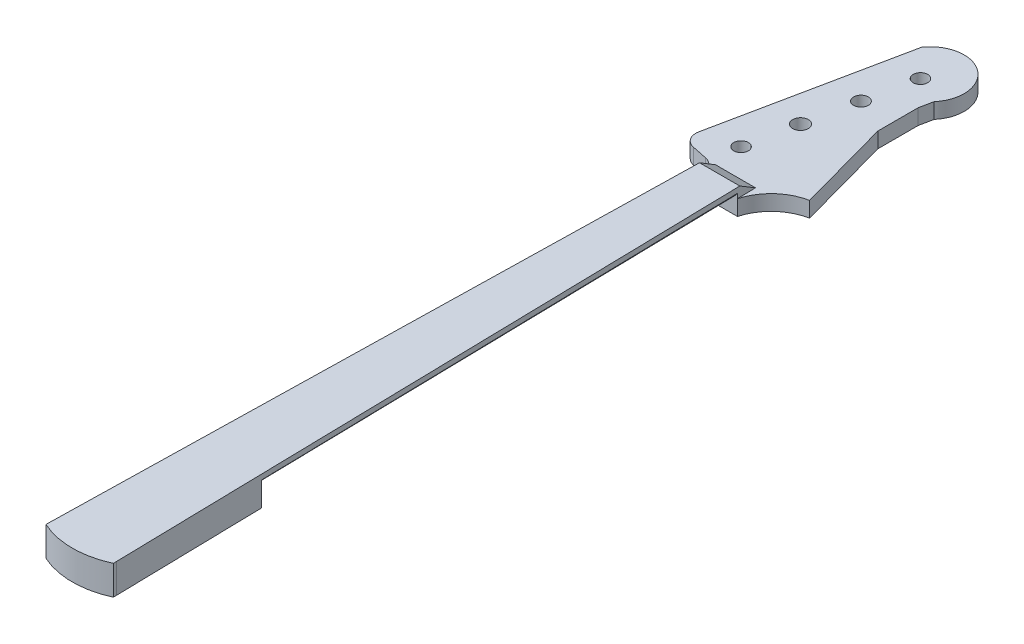
SolidWorks part; units mm, degrees
ref_plane "Front Plane" through (0, 0, 0) normal (0, 0, 1) x (1, 0, 0)
ref_plane "Top Plane" through (0, 0, 0) normal (0, 1, 0) x (1, 0, 0)
ref_plane "Right Plane" through (0, 0, 0) normal (1, 0, 0) x (0, 0, -1)
sketch "Sketch1" plane through (0, 0, 0) normal (0, 0, 1) x (1, 0, 0)
  line L0 (-19.05, 0) -> (19.05, 0)
  line L1 (19.05, 0) -> (19.05, -4.826)
  line L2 (19.05, -4.826) -> (-19.05, -4.826)
  line L3 (-19.05, -4.826) -> (-19.05, 0)
  point P3 (-19.5158, 0.0762)
  point P6 (0, 0)
  dimension "D1" = 38.1
  dimension "D2" = 4.826
ref_plane "Plane1" through (0, 0, 598.4875) normal (0, 0, 1) x (1, 0, 0)
sketch "Sketch2" plane through (0, 0, 598.4875) normal (0, 0, 1) x (1, 0, 0)
  line L0 (19.05, -4.826) -> (-19.05, -4.826) construction
  line L1 (-31.75, 0) -> (31.75, 0)
  line L2 (-31.75, 0) -> (-31.75, -4.826)
  line L3 (-31.75, -4.826) -> (31.75, -4.826)
  line L4 (31.75, 0) -> (31.75, -4.826)
  line L5 (-19.05, 0) -> (19.05, 0) construction
  point P8 (0, 0)
  dimension "D1" = 63.5
loft "Loft1" add profiles "Sketch1", "Sketch2" connector at (-19.05, 0, 0) connector at (-31.75, 0, 598.4875)
sketch "Sketch3" plane through (0, 0, 0) normal (0, 0, -1) x (-1, 0, 0)
  line L0 (19.05, -4.826) -> (-19.05, -4.826) construction
  line L1 (19.05, -4.826) -> (-19.05, -4.826)
  arc A0 (-19.05, -4.826) -> (19.05, -4.826) centre (0, 7.5791) ccw
  point P3 (0, 3.4506)
  dimension "D1" = 22.733
ref_plane "Plane2" through (0, 0, 458.7875) normal (0, 0, 1) x (1, 0, 0)
sketch "Sketch5" plane through (0, -4.826, 0) normal (0, -1, 0) x (1, 0, 0)
  line L0 (19.05, 0) -> (31.75, 598.4875) construction
  line L1 (28.7855, 458.7875) -> (31.75, 598.4875)
  line L2 (-19.05, 0) -> (-31.75, 598.4875) construction
  line L3 (-28.7855, 458.7875) -> (-31.75, 598.4875)
  line L4 (-31.75, 598.4875) -> (31.75, 598.4875)
  line L5 (-28.7855, 458.7875) -> (28.7855, 458.7875)
  line L6 (13.6811, 458.7875) -> (-13.6811, 458.7875) construction
extrude "Boss-Extrude1" add sketch "Sketch5" along normal blind 22.86
sketch "Sketch4" plane through (0, 0, 458.7875) normal (0, 0, 1) x (1, 0, 0)
  line L3 (-28.7855, -4.826) -> (28.7855, -4.826)
  line L4 (-19.05, -4.826) -> (19.05, -4.826) construction
  line L5 (-28.7855, -4.826) -> (28.7855, -4.826) construction
  arc A1 (-28.7855, -4.826) -> (28.7855, -4.826) centre (0, 18.034) ccw
  point P2 (27.5175, -4.826)
  point P3 (-28.7855, -4.826)
  point P6 (0, -4.826)
  point P9 (0, -4.826)
  point P11 (0, 17.595)
  dimension "D1" = 22.86
loft "Loft2" add profiles "Sketch4", "Sketch3" connector at (-28.7855, -4.826, 458.7875) connector at (-19.05, -4.826, 0)
sketch "Sketch6" plane through (0, 0, 0) normal (0, 1, 0) x (1, 0, 0)
  line L0 (-31.75, -598.4875) -> (-31.75, -601.5355)
  line L2 (31.75, -598.4875) -> (31.75, -601.5355)
  line L5 (31.75, -598.4875) -> (-31.75, -598.4875) construction
  line L6 (31.75, -598.4875) -> (-31.75, -598.4875)
  arc A0 (-31.75, -601.5355) -> (31.75, -601.5355) centre (0, -532.8689) ccw
  point P2 (0, -608.5205)
  point P3 (-31.75, -601.5355)
  dimension "D1" = 6.985
  dimension "D2" = 3.048
extrude "Boss-Extrude2" add sketch "Sketch6" against normal up to surface (27.686 mm away) up to face at (0, -27.686, 528.6375)
ref_plane "Plane3" through (0, -23.749, 0) normal (0, 1, 0) x (1, 0, 0)
sketch "Sketch7" plane through (0, -23.749, 0) normal (0, 1, 0) x (1, 0, 0)
  line L0 (-53.7966, 36.3949) -> (-17.8583, 210.525)
  line L1 (-43.9257, 21.39) -> (-29.183, 18.3473)
  line L2 (32.5646, 172.0943) -> (29.9976, 159.6564)
  line L3 (-19.05, 0) -> (19.05, 0)
  line L4 (19.05, 0) -> (19.1268, -3.6195) construction
  line L5 (19.05, 0) -> (31.75, -598.4875) construction
  line L6 (19.1268, -3.6195) -> (-19.1268, -3.6195) construction
  line L7 (-19.05, 0) -> (-31.75, -598.4875) construction
  line L8 (-19.1268, -3.6195) -> (-19.05, 0) construction
  line L9 (-14.859, 0) -> (-14.859, -3.6195) construction
  line L10 (-4.7244, 0) -> (-4.7244, -3.6195) construction
  line L11 (4.572, 0) -> (4.572, -3.6195) construction
  line L12 (14.097, 0) -> (14.097, -3.6195) construction
  line L13 (-14.859, 0) -> (-14.859, 44.196) construction
  line L14 (-4.7244, 0) -> (-4.7244, 90.7136) construction
  line L15 (4.572, 0) -> (4.572, 137.9775) construction
  line L16 (14.097, 0) -> (14.097, 184.4951) construction
  line L17 (-21.7234, 44.196) -> (7.2326, 184.4951) construction
  line L18 (-19.05, 5.9095) -> (-19.05, 0)
  line L19 (29.9976, 159.6564) -> (29.9976, 121.5564)
  line L20 (29.9976, 121.5564) -> (54.4767, 32.6564)
  arc A1 (32.5646, 172.0943) -> (-17.8583, 210.525) centre (8.4403, 192.7361) ccw
  circle A2 centre (-21.7234, 44.196) radius 6.8643
  circle A3 centre (-12.1227, 90.7136) radius 7.3983
  circle A4 centre (-2.368, 137.9775) radius 6.94
  circle A5 centre (7.2326, 184.4951) radius 6.8643
  arc A7 (19.05, 0) -> (54.4767, 32.6564) centre (63.1003, -12.2429) cw
  arc A8 (-29.183, 18.3473) -> (-19.05, 5.9095) centre (-31.75, 5.9095) cw
  arc A9 (-53.7966, 36.3949) -> (-43.9257, 21.39) centre (-41.3587, 33.8279) ccw
  point P5 (-4.7244, 90.7136)
  point P27 (4.572, 137.9775)
  point P39 (14.097, 178.963)
  point P40 (14.097, 184.4951)
  point P45 (-19.05, 16.256)
  point P48 (-56.3636, 23.9571)
  point P49 (-14.859, 44.196)
  dimension "D4" = 13.7287
  dimension "D14" = 14.7966
  dimension "D16" = 63.5
  dimension "D19" = 45.72
  dimension "D20" = 12.7
  dimension "D1" = 190.5
  dimension "D2" = 38.1
  dimension "D3" = 57.15
  dimension "D5" = 3.6195
  dimension "D6" = 4.191
  dimension "D7" = 10.1346
  dimension "D8" = 19.431
  dimension "D9" = 28.956
  dimension "D10" = 47.498
  dimension "D11" = 95.758
  dimension "D12" = 143.256
  dimension "D13" = 44.196
  dimension "D15" = 16.256
  dimension "D17" = 12.7
  dimension "D18" = 76.2
  dimension "D21" = 88.9
  dimension "D22" = 38.1
  dimension "D23" = 172.0943
  dimension "D24" = 164.605
extrude "Boss-Extrude3" add sketch "Sketch7" along normal blind 14.5542
sketch "Sketch8" plane through (-19.05, 0, 0) normal (-1, 0, 0) x (0, 0, 1)
  line L0 (0, 0) -> (-2.286, 0)
  line L1 (-2.286, 0) -> (-17.399, -9.1948)
  line L3 (-5.9095, -9.1948) -> (-18.3473, -9.1948) construction
  line L4 (-17.399, -9.1948) -> (0, -9.1948)
  line L5 (0, -9.1948) -> (0, 0)
  dimension "D1" = 2.286
  dimension "D2" = 17.399
extrude "Boss-Extrude4" add sketch "Sketch8" against normal up to surface (37.7308 mm away) up to face at (25.6719, -13.9337, 312.0571)
